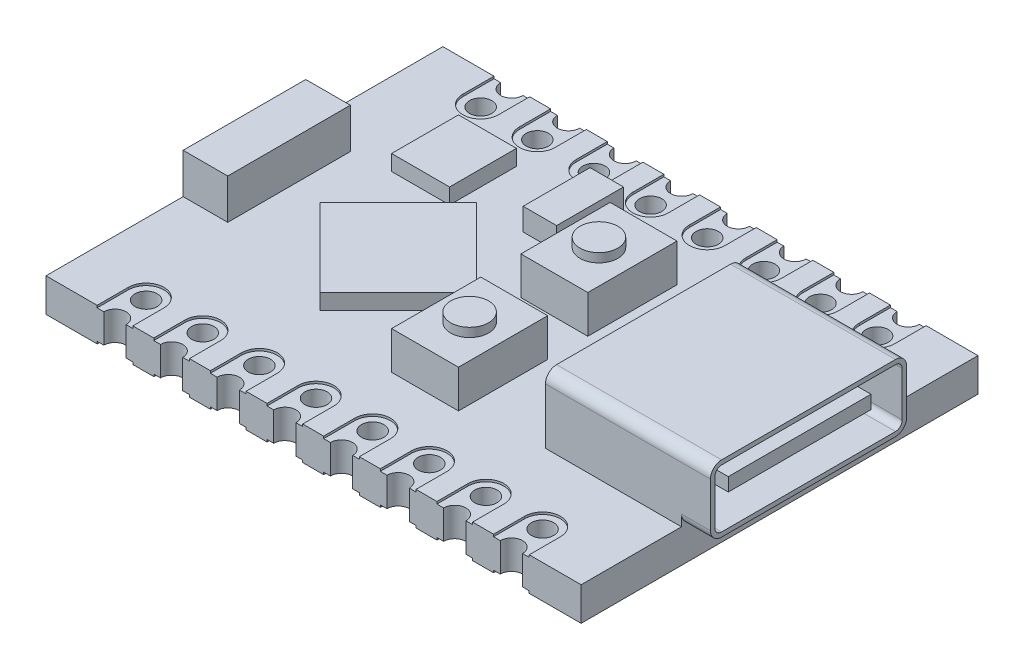
SolidWorks part; units mm, degrees
ref_plane "Front Plane" through (0, 0, 0) normal (0, 0, 1) x (1, 0, 0)
ref_plane "Top Plane" through (0, 0, 0) normal (0, 1, 0) x (1, 0, 0)
ref_plane "Right Plane" through (0, 0, 0) normal (1, 0, 0) x (0, 0, -1)
sketch "Sketch1" plane through (0, 0, 0) normal (0, 1, 0) x (1, 0, 0)
  line L1 (0, 0) -> (24, 0)
  line L2 (0, 0) -> (0, 17.8)
  line L3 (0, 17.8) -> (24, 17.8)
  line L4 (24, 0) -> (24, 17.8)
  dimension "D1" = 24
  dimension "D2" = 17.8
sketch "Sketch2" plane through (0, 0, 0) normal (0, 1, 0) x (1, 0, 0)
  line L0 (0, 0) -> (0, 17.8) construction
  line L1 (0, 0) -> (0, 17.8)
  line L2 (0, 17.8) -> (24, 17.8) construction
  line L3 (0, 17.8) -> (24, 17.8)
  line L4 (24, 0) -> (24, 17.8) construction
  line L5 (24, 0) -> (24, 17.8)
  line L6 (0, 0) -> (24, 0) construction
  line L7 (0, 0) -> (24, 0)
extrude "Boss-Extrude1" add sketch "Sketch2" against normal blind 1.5
sketch "Sketch3" plane through (0, 0, 0) normal (0, 1, 0) x (1, 0, 0)
  line L0 (0, 8.9) -> (24, 8.9) construction
  line L1 (0, 0) -> (0, 17.8) construction
  line L2 (24, 0) -> (24, 17.8) construction
  line L4 (2, 11.65) -> (0, 11.65)
  line L5 (2, 11.65) -> (2, 6.15)
  line L6 (2, 6.15) -> (0, 6.15)
  line L7 (0, 11.65) -> (0, 6.15)
  line L8 (2, 11.65) -> (0, 6.15) construction
  line L9 (2, 6.15) -> (0, 11.65) construction
  point P6 (1, 8.9)
  dimension "D1" = 5.5
  dimension "D2" = 2
extrude "Boss-Extrude2" add sketch "Sketch3" along normal blind 1.8
sketch "Sketch4" plane through (0, 0, 0) normal (0, 1, 0) x (1, 0, 0)
  line L0 (2, 6.15) -> (2, 11.65) construction
  line L3 (4, 8.3) -> (7.5, 11.8)
  line L4 (4, 8.3) -> (7.5, 4.8)
  line L5 (7.5, 11.8) -> (11, 8.3)
  line L6 (7.5, 4.8) -> (11, 8.3)
  line L7 (0, 17.8) -> (24, 17.8) construction
  dimension "D1" = 6
  dimension "D2" = 7
  dimension "D3" = 7
  dimension "D4" = 2
extrude "Boss-Extrude3" add sketch "Sketch4" along normal blind 0.7
sketch "Sketch5" plane through (0, 0, 0) normal (0, 1, 0) x (1, 0, 0)
  line L0 (0, 17.8) -> (24, 17.8) construction
  line L1 (3.7, 14.8) -> (6.3, 14.8)
  line L2 (3.7, 14.8) -> (3.7, 11.8)
  line L3 (3.7, 11.8) -> (6.3, 11.8)
  line L4 (6.3, 14.8) -> (6.3, 11.8)
  line L5 (0, 0) -> (0, 17.8) construction
  dimension "D1" = 2.6
  dimension "D2" = 3
  dimension "D3" = 3
  dimension "D4" = 3.7
extrude "Boss-Extrude4" add sketch "Sketch5" along normal blind 0.7
sketch "Sketch6" plane through (0, 0, 0) normal (0, 1, 0) x (1, 0, 0)
  line L0 (0, 0) -> (0, 17.8) construction
  line L1 (9, 15.4) -> (10.5, 15.4)
  line L2 (9, 15.4) -> (9, 12.4)
  line L3 (9, 12.4) -> (10.5, 12.4)
  line L4 (10.5, 15.4) -> (10.5, 12.4)
  line L5 (0, 17.8) -> (24, 17.8) construction
  dimension "D1" = 1.5
  dimension "D2" = 3
  dimension "D3" = 9
  dimension "D4" = 2.4
extrude "Boss-Extrude5" add sketch "Sketch6" along normal blind 1
sketch "Sketch7" plane through (0, 0, 0) normal (0, 1, 0) x (1, 0, 0)
  line L0 (0, 17.8) -> (24, 17.8) construction
  line L1 (11.5, 13.8) -> (14.5, 13.8)
  line L2 (11.5, 13.8) -> (11.5, 9.8)
  line L3 (11.5, 9.8) -> (14.5, 9.8)
  line L4 (14.5, 13.8) -> (14.5, 9.8)
  line L6 (24, 0) -> (24, 17.8) construction
  dimension "D1" = 3
  dimension "D2" = 4
  dimension "D3" = 4
  dimension "D4" = 9.5
extrude "Boss-Extrude6" add sketch "Sketch7" along normal blind 1.7
sketch "Sketch8" plane through (0, 1.7, 0) normal (0, 1, 0) x (1, 0, 0)
  line L0 (13, 11.8) -> (13, 13.8) construction
  line L1 (14.5, 13.8) -> (11.5, 13.8) construction
  line L2 (13, 11.8) -> (11.5, 11.8) construction
  line L3 (11.5, 13.8) -> (11.5, 9.8) construction
  circle A0 centre (13, 11.8) radius 0.85
  dimension "D1" = 1.7
extrude "Boss-Extrude7" add sketch "Sketch8" along normal blind 0.4
ref_plane "Plane1" through (0, 0, -8.9) normal (0, 0, -1) x (-1, 0, 0)
mirror "Mirror1" about plane through (0, 0, -8.9) normal (0, 0, -1) of "Boss-Extrude7", "Boss-Extrude6"
sketch "Sketch9" plane through (0, 0, 0) normal (0, 1, 0) x (1, 0, 0)
  line L0 (3.0931, 16.4027) -> (0, 16.4027) construction
  line L1 (0, 0) -> (0, 17.8) construction
  line L2 (0, 16.4027) -> (24, 16.4027) construction
  line L3 (24, 0) -> (24, 17.8) construction
  circle A0 centre (3.0931, 16.4027) radius 0.5
  circle A1 centre (5.6331, 16.4027) radius 0.5
  circle A2 centre (8.1731, 16.4027) radius 0.5
  circle A3 centre (10.7131, 16.4027) radius 0.5
  circle A4 centre (13.2531, 16.4027) radius 0.5
  circle A5 centre (15.7931, 16.4027) radius 0.5
  circle A6 centre (18.3331, 16.4027) radius 0.5
  circle A7 centre (20.8731, 16.4027) radius 0.5
  dimension "D1" = 1
  dimension "D2" = 8
extrude "Cut-Extrude1" cut sketch "Sketch9" against normal through all
sketch "Sketch10" plane through (0, 0, 0) normal (0, 1, 0) x (1, 0, 0)
  line L0 (2.2931, 16.4027) -> (2.2931, 17.8)
  line L1 (0, 17.8) -> (24, 17.8) construction
  line L2 (3.8931, 16.4027) -> (3.8931, 17.8)
  line L3 (3.8931, 17.8) -> (2.2931, 17.8)
  circle A0 centre (3.0931, 16.4027) radius 0.5 construction
  circle A1 centre (3.0931, 16.4027) radius 0.5 construction
  arc A2 (2.2931, 16.4027) -> (3.8931, 16.4027) centre (3.0931, 16.4027) ccw
  circle A3 centre (3.0931, 17.8) radius 0.5 construction
  circle A4 centre (3.0931, 16.4027) radius 0.8 construction
  dimension "D2" = 1
  dimension "D1" = 0.3
extrude "Cut-Extrude2" cut sketch "Sketch10" against normal blind 0.1
pattern_linear "LPattern1" count 8 spacing 2.54 along (1, 0, 0) of "Cut-Extrude2"
sketch "Sketch11" plane through (0, 0, 0) normal (0, 1, 0) x (1, 0, 0)
  circle A0 centre (3.0931, 17.8) radius 0.5 construction
  circle A1 centre (3.0931, 17.8) radius 0.5
  circle A2 centre (5.6331, 17.8) radius 0.5
  circle A3 centre (8.1731, 17.8) radius 0.5
  circle A4 centre (10.7131, 17.8) radius 0.5
  circle A5 centre (13.2531, 17.8) radius 0.5
  circle A6 centre (15.7931, 17.8) radius 0.5
  circle A7 centre (18.3331, 17.8) radius 0.5
  circle A8 centre (20.8731, 17.8) radius 0.5
  dimension "D1" = 8
extrude "Cut-Extrude3" cut sketch "Sketch11" against normal through all
ref_plane "Plane2" through (0, -0.75, 0) normal (0, 1, 0) x (1, 0, 0)
mirror "Mirror2" about plane through (0, -0.75, 0) normal (0, 1, 0) of "LPattern1"
mirror "Mirror3" about plane through (0, 0, -8.9) normal (0, 0, -1) of "Cut-Extrude3", "Mirror2", "LPattern1", "Cut-Extrude2", "Cut-Extrude1"
ref_plane "Plane3" through (25.3, 0, 0) normal (1, 0, 0) x (0, 0, -1)
sketch "Sketch12" plane through (25.3, 0, 0) normal (1, 0, 0) x (0, 0, -1)
  line L0 (8.9, 0) -> (8.9, 3) construction
  line L1 (0, 0) -> (17.8, 0) construction
  line L2 (4.5, 1.5) -> (13.3, 1.5) construction
  line L4 (4.5, 3) -> (13.3, 3)
  line L5 (4.5, 3) -> (4.5, 0)
  line L6 (4.5, 0) -> (13.3, 0)
  line L7 (13.3, 3) -> (13.3, 0)
  line L8 (4.5, 3) -> (13.3, 0) construction
  line L9 (4.5, 0) -> (13.3, 3) construction
  point P4 (8.9, 1.5)
  point P7 (8.9, 1.5)
  dimension "D1" = 3
  dimension "D2" = 8.8
extrude "Boss-Extrude8" add sketch "Sketch12" against normal blind 7.4
fillet "Fillet1" radius 0.5 4 edges at (24.65, 0, -4.5) (24.65, 0, -13.3) (21.6, 3, -13.3) (21.6, 3, -4.5)
sketch "Sketch13" plane through (25.3, 0, 0) normal (1, 0, 0) x (0, 0, -1)
  line L0 (4.7, 2.5) -> (4.7, 0.5)
  line L1 (5, 0.2) -> (12.8, 0.2)
  line L2 (13.1, 0.5) -> (13.1, 2.5)
  line L3 (12.8, 2.8) -> (5, 2.8)
  line L4 (4.5, 2.5) -> (4.5, 0.5)
  line L5 (5, 0) -> (12.8, 0)
  line L6 (13.3, 0.5) -> (13.3, 2.5)
  line L7 (12.8, 3) -> (5, 3)
  line L8 (4.5, 2.5) -> (4.5, 0.5)
  line L9 (5, 0) -> (12.8, 0)
  line L10 (13.3, 0.5) -> (13.3, 2.5)
  line L11 (12.8, 3) -> (5, 3)
  arc A0 (5, 2.8) -> (4.7, 2.5) centre (5, 2.5) ccw
  arc A1 (4.7, 0.5) -> (5, 0.2) centre (5, 0.5) ccw
  arc A2 (12.8, 0.2) -> (13.1, 0.5) centre (12.8, 0.5) ccw
  arc A3 (13.1, 2.5) -> (12.8, 2.8) centre (12.8, 2.5) ccw
  arc A4 (4.5, 0.5) -> (5, 0) centre (5, 0.5) ccw
  arc A5 (12.8, 0) -> (13.3, 0.5) centre (12.8, 0.5) ccw
  arc A6 (13.3, 2.5) -> (12.8, 3) centre (12.8, 2.5) ccw
  arc A7 (5, 3) -> (4.5, 2.5) centre (5, 2.5) ccw
  arc A8 (4.5, 0.5) -> (5, 0) centre (5, 0.5) ccw
  arc A9 (12.8, 0) -> (13.3, 0.5) centre (12.8, 0.5) ccw
  arc A10 (13.3, 2.5) -> (12.8, 3) centre (12.8, 2.5) ccw
  arc A11 (5, 3) -> (4.5, 2.5) centre (5, 2.5) ccw
  dimension "D1" = 0
  dimension "D2" = 0.2
extrude "Cut-Extrude4" cut sketch "Sketch13" against normal blind 6.4 contours L2 A3 L3 A0 L0 A1 L1 A2 region at (25.3, 1.5, -8.9)
sketch "Sketch14" plane through (18.9, 0, 0) normal (1, 0, 0) x (0, 0, -1)
  line L0 (5.7, 1.8) -> (5.7, 1.2)
  line L1 (5.7, 1.2) -> (12.1, 1.2)
  line L2 (12.1, 1.2) -> (12.1, 1.8)
  line L3 (12.1, 1.8) -> (5.7, 1.8)
  line L4 (13.1, 0.5) -> (13.1, 2.5)
  line L5 (12.8, 2.8) -> (5, 2.8)
  line L6 (4.7, 2.5) -> (4.7, 0.5)
  line L7 (5, 0.2) -> (12.8, 0.2)
  line L8 (13.1, 0.5) -> (13.1, 2.5)
  line L9 (12.8, 2.8) -> (5, 2.8)
  line L10 (4.7, 2.5) -> (4.7, 0.5)
  line L11 (5, 0.2) -> (12.8, 0.2)
  arc A0 (5.7, 1.8) -> (5.7, 1.8) centre (5.7, 1.8) ccw
  arc A1 (5.7, 1.2) -> (5.7, 1.2) centre (5.7, 1.2) ccw
  arc A2 (12.1, 1.2) -> (12.1, 1.2) centre (12.1, 1.2) ccw
  arc A3 (12.1, 1.8) -> (12.1, 1.8) centre (12.1, 1.8) ccw
  arc A4 (13.1, 2.5) -> (12.8, 2.8) centre (12.8, 2.5) ccw
  arc A5 (5, 2.8) -> (4.7, 2.5) centre (5, 2.5) ccw
  arc A6 (4.7, 0.5) -> (5, 0.2) centre (5, 0.5) ccw
  arc A7 (12.8, 0.2) -> (13.1, 0.5) centre (12.8, 0.5) ccw
  arc A8 (13.1, 2.5) -> (12.8, 2.8) centre (12.8, 2.5) ccw
  arc A9 (5, 2.8) -> (4.7, 2.5) centre (5, 2.5) ccw
  arc A10 (4.7, 0.5) -> (5, 0.2) centre (5, 0.5) ccw
  arc A11 (12.8, 0.2) -> (13.1, 0.5) centre (12.8, 0.5) ccw
  dimension "D1" = 0
  dimension "D2" = 1
extrude "Boss-Extrude9" add sketch "Sketch14" along normal blind 6 contours L2 L3 L0 L1 region at (18.9, 1.5, -8.9)
sketch "Sketch15" plane through (0, 0, 0) normal (-1, 0, 0) x (0, 0, 1)
  line L0 (-6.15, 1.8) -> (-6.15, 0) construction
  line L1 (-11.65, 0) -> (-6.15, 0)
  line L2 (-11.65, 0) -> (-11.65, 0.01)
  line L3 (-11.65, 0.01) -> (-6.15, 0.01)
  line L4 (-6.15, 0) -> (-6.15, 0.01)
  dimension "D1" = 0.01
extrude "Cut-Extrude5" cut sketch "Sketch15" against normal blind 0.01
